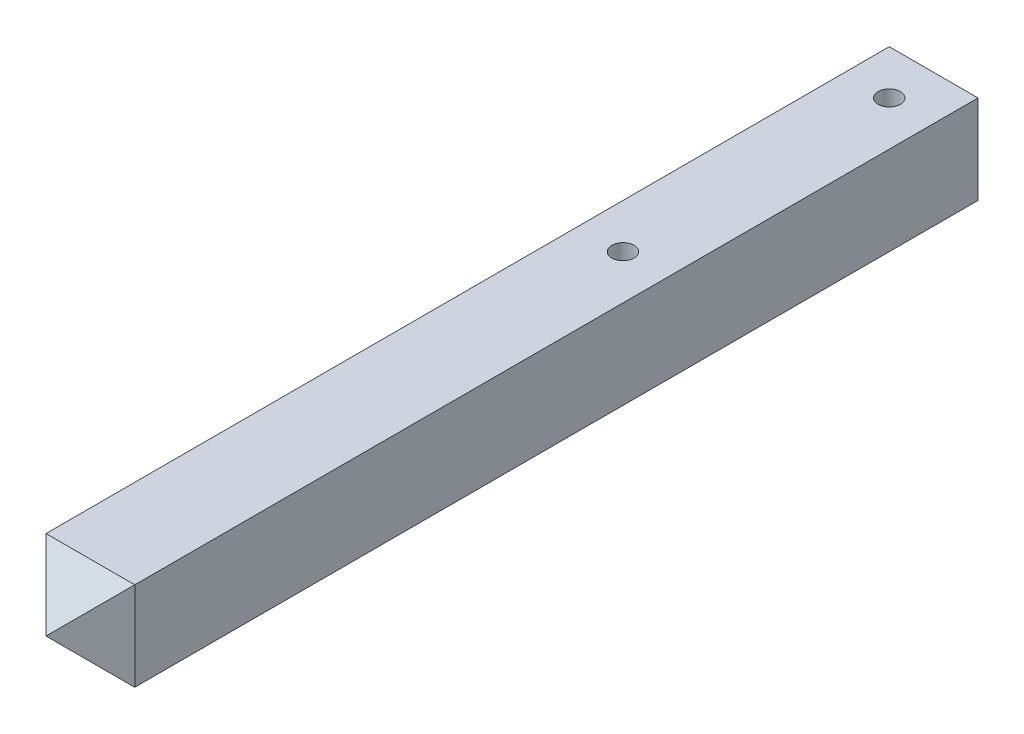
SolidWorks part; units mm, degrees
ref_plane "Front Plane" through (0, 0, 0) normal (0, 0, 1) x (1, 0, 0)
ref_plane "Top Plane" through (0, 0, 0) normal (0, 1, 0) x (1, 0, 0)
ref_plane "Right Plane" through (0, 0, 0) normal (1, 0, 0) x (0, 0, -1)
sketch "Sketch1" plane through (0, 0, 0) normal (0, 1, 0) x (1, 0, 0)
  line L1 (0, 0) -> (20, 0)
  line L2 (0, 0) -> (0, -200)
  line L3 (0, -200) -> (20, -200)
  line L4 (20, 0) -> (20, -200)
  circle A0 centre (10, -10) radius 2.5
  circle A1 centre (10, -70) radius 2.5
  dimension "D3" = 5
  dimension "D4" = 5
  dimension "D5" = 60
  dimension "D6" = 10
  dimension "D1" = 20
  dimension "D2" = 200
extrude "Boss-Extrude1" add sketch "Sketch1" along normal blind 20
chamfer "Chamfer1" distance 10 angle 45 4 edges at (20, 10, 200) (10, 0, 200) (0, 10, 200) (10, 20, 200)
